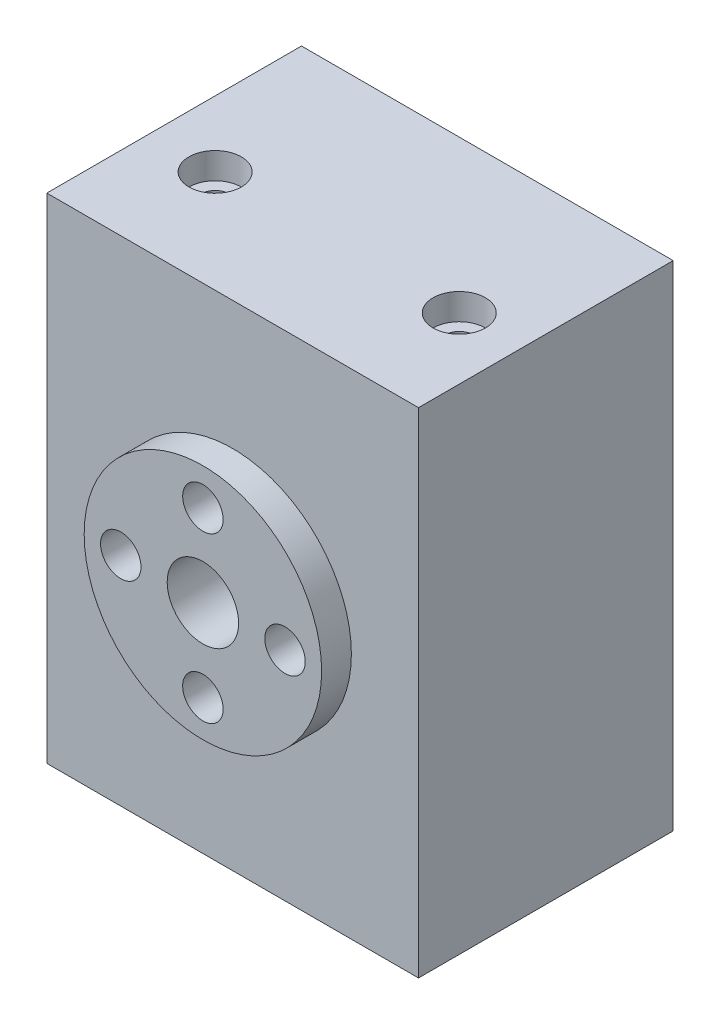
SolidWorks part; units mm, degrees
ref_plane "Front Plane" through (0, 0, 0) normal (0, 0, 1) x (1, 0, 0)
ref_plane "Top Plane" through (0, 0, 0) normal (0, 1, 0) x (1, 0, 0)
ref_plane "Right Plane" through (0, 0, 0) normal (1, 0, 0) x (0, 0, -1)
sketch "Sketch1" plane through (0, 0, 0) normal (0, 0, 1) x (1, 0, 0)
  circle A0 centre (0, 0) radius 9.975
  dimension "D1" = 19.95
extrude "Boss-Extrude1" add sketch "Sketch1" along normal blind 2.5
sketch "Sketch3" plane through (0, 0, 0) normal (0, 0, -1) x (-1, 0, 0)
  line L0 (15.615, 20.75) -> (15.615, -20.75)
  line L1 (-12.615, 17.75) -> (12.615, 17.75)
  line L2 (-12.615, 17.75) -> (-12.615, -17.75)
  line L3 (-12.615, -17.75) -> (12.615, -17.75)
  line L4 (12.615, 17.75) -> (12.615, -17.75)
  line L5 (-12.615, 17.75) -> (12.615, -17.75) construction
  line L6 (-12.615, -17.75) -> (12.615, 17.75) construction
  line L7 (-15.615, -20.75) -> (15.615, -20.75)
  line L8 (-15.615, 20.75) -> (-15.615, -20.75)
  line L9 (-15.615, 20.75) -> (15.615, 20.75)
  point P0 (0, 0)
  dimension "D1" = 35.5
  dimension "D2" = 25.23
  dimension "D3" = 3
extrude "Boss-Extrude4" add sketch "Sketch3" along normal blind 2.5 contours L2 L1 L4 L3
extrude "Boss-Extrude5" add sketch "Sketch3<5>" along normal blind 21.4
sketch "Sketch3<5>" plane through (0, 0, 0) normal (0, 0, -1) x (-1, 0, 0) same geometry as "Sketch3"
sketch "Sketch4" plane through (0, 0, -2.5) normal (0, 0, -1) x (-1, 0, 0)
  line L1 (12.615, 17.75) -> (7.415, 17.75)
  line L2 (12.615, 17.75) -> (12.615, 16.65)
  line L3 (12.615, 16.65) -> (7.415, 16.65)
  line L4 (7.415, 17.75) -> (7.415, 16.65)
  line L5 (-12.615, 17.75) -> (-7.415, 17.75)
  line L6 (-12.615, 17.75) -> (-12.615, 16.65)
  line L7 (-12.615, 16.65) -> (-7.415, 16.65)
  line L8 (-7.415, 17.75) -> (-7.415, 16.65)
  line L9 (12.615, -17.75) -> (9.415, -17.75)
  line L10 (12.615, -17.75) -> (12.615, -16.05)
  line L11 (12.615, -16.05) -> (9.415, -16.05)
  line L12 (9.415, -17.75) -> (9.415, -16.05)
  line L13 (-12.615, -17.75) -> (-9.415, -17.75)
  line L14 (-12.615, -17.75) -> (-12.615, -16.05)
  line L15 (-12.615, -16.05) -> (-9.415, -16.05)
  line L16 (-9.415, -17.75) -> (-9.415, -16.05)
  dimension "D1" = 1.1
  dimension "D2" = 5.2
  dimension "D3" = 5.2
  dimension "D4" = 1.1
  dimension "D5" = 3.2
  dimension "D6" = 1.7
  dimension "D7" = 3.2
  dimension "D8" = 1.7
extrude "Boss-Extrude6" add sketch "Sketch4" along normal blind 18.9 contours L2 L1 L4 L3 | L6 L5 L8 L7 | L10 L9 L12 L11 | L14 L13 L16 L15
sketch "Sketch6" plane through (0, 0, -2.5) normal (0, 0, -1) x (-1, 0, 0)
  line L1 (9.415, -17.75) -> (-9.415, -17.75)
  line L2 (9.415, -17.75) -> (9.415, -16.05)
  line L3 (9.415, -16.05) -> (-9.415, -16.05)
  line L4 (-9.415, -17.75) -> (-9.415, -16.05)
extrude "Boss-Extrude7" add sketch "Sketch6" along normal blind 5.3
sketch "Sketch2" plane through (0, 0, 2.5) normal (0, 0, 1) x (1, 0, 0)
  circle A0 centre (0, 0) radius 7 construction
  circle A1 centre (7, 0) radius 1.6
  circle A2 centre (0, -7) radius 1.6
  circle A3 centre (-7, 0) radius 1.6
  circle A4 centre (0, 7) radius 1.6
  point P14 (0, 0)
  dimension "D1" = 14
  dimension "D2" = 3.2
  dimension "D3" = 4
extrude "Cut-Extrude1" cut sketch "Sketch2" against normal blind 37
hole_wizard "CBORE for M3 Hex Socket Head Cap Screw1" positions "Sketch7" profile "Sketch8" counterbore size "M3" standard "ISO" end condition through all
sketch "Sketch7" plane through (0, 0, -2.5) normal (0, 0, -1) x (-1, 0, 0)
  circle A0 centre (0, 0) radius 6.9 construction
  point P0 (0, 6.9)
  point P4 (-6.9, 0)
  point P6 (6.9, 0)
  point P9 (0, -6.9)
sketch "Sketch8" plane through (0, 6.9, -2.5) normal (1, 0, 0) x (0, 1, 0)
  line L0 (0, 0) -> (0, 5)
  line L1 (0, 5) -> (1.7, 5)
  line L3 (1.7, 5) -> (1.7, 2.2)
  line L4 (1.7, 2.2) -> (3, 2.2)
  line L5 (3, 2.2) -> (3, 0)
  line L7 (3, 0) -> (0, 0)
  line L11 (0, -6.35) -> (0, 107.95) construction
  dimension "Thru Hole Dia." = 3.4
  dimension "Thru Hole Depth" = 5
  dimension "C'Bore Dia." = 6
  dimension "C'Bore Depth" = 2.2
hole_wizard "CBORE for M2 Hex Socket Head Cap Screw1" positions "Sketch9" profile "Sketch10" counterbore size "M2" standard "ISO" end condition up to next
sketch "Sketch9" plane through (0, 20.75, 0) normal (0, 1, 0) x (1, 0, 0)
  point P0 (-10.0818, 8.61)
  point P2 (10.4297, 8.61)
sketch "Sketch10" plane through (-10.0818, 20.75, -8.61) normal (1, 0, 0) x (0, 0, 1)
  line L0 (0, 0) -> (0, 4.1)
  line L1 (0, 4.1) -> (1.2, 4.1)
  line L3 (1.2, 4.1) -> (1.2, 2.2)
  line L4 (1.2, 2.2) -> (2.2, 2.2)
  line L5 (2.2, 2.2) -> (2.2, 0)
  line L7 (2.2, 0) -> (0, 0)
  line L11 (0, -6.35) -> (0, 107.95) construction
  dimension "Thru Hole Dia." = 2.4
  dimension "Thru Hole Depth" = 4.1
  dimension "C'Bore Dia." = 4.4
  dimension "C'Bore Depth" = 2.2
hole_wizard "CBORE for M2 Hex Socket Head Cap Screw2" positions "Sketch15" profile "Sketch16" counterbore size "M2" standard "ISO"
sketch "Sketch15" plane through (0, -20.75, 0) normal (0, -1, 0) x (-1, 0, 0)
  point P0 (-10.1683, 4.86)
  point P8 (10.3453, 4.86)
sketch "Sketch16" plane through (10.1683, -20.75, -4.86) normal (1, 0, 0) x (0, 0, -1)
  line L0 (0, 0) -> (0, 5.5811)
  line L1 (0, 5.5811) -> (1.3, 4.8)
  line L2 (1.3, 4.8) -> (1.3, 3.5)
  line L3 (1.3, 3.5) -> (2.2, 3.5)
  line L4 (2.2, 3.5) -> (2.2, 0)
  line L5 (2.2, 0) -> (0, 0)
  line L10 (0, 5.5811) -> (-1.3, 4.8) construction
  line L11 (0, -6.35) -> (0, 107.95) construction
  dimension "Hole Dia." = 2.6
  dimension "Hole Depth" = 4.8
  dimension "C'Bore Dia." = 4.4
  dimension "C'Bore Depth" = 3.5
  dimension "Drill Angle" = 118
sketch "Sketch17" plane through (0, 0, -2.5) normal (0, 0, -1) x (-1, 0, 0)
  circle A0 centre (0, 0) radius 3
  dimension "D1" = 6
extrude "Cut-Extrude2" cut sketch "Sketch17" against normal blind 10
